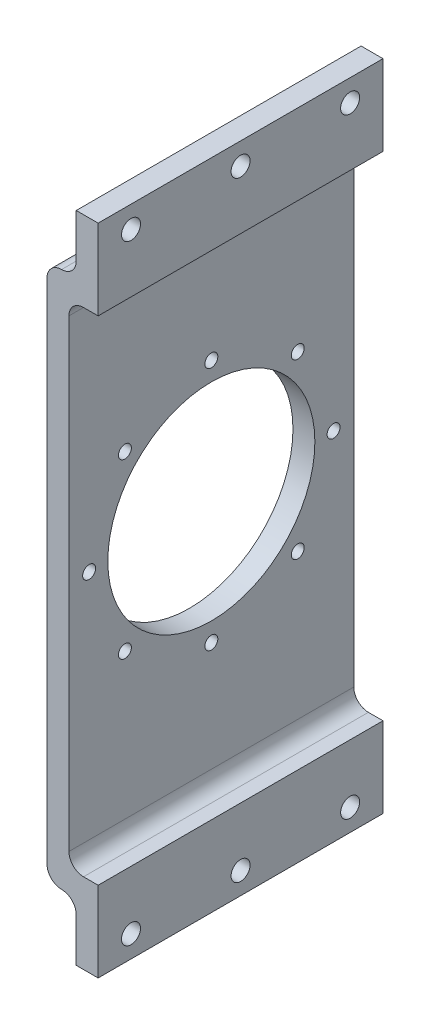
SolidWorks part; units mm, degrees
other "Markup1"
sketch "Sketch9" plane through (-7.62, -27.94, -49.53) normal (-1, 0, 0) x (0, 0, 1)
sketch "Sketch12" plane through (-7.62, -27.94, -49.53) normal (-1, 0, 0) x (0, 0, 1)
material "ABS"
ref_plane "Front Plane" through (0, 0, 0) normal (0, 0, 1) x (1, 0, 0)
ref_plane "Top Plane" through (0, 0, 0) normal (0, 1, 0) x (1, 0, 0)
ref_plane "Right Plane" through (0, 0, 0) normal (1, 0, 0) x (0, 0, -1)
sketch "Sketch1" plane through (0, 0, 0) normal (0, 0, 1) x (1, 0, 0)
  line L0 (0, 0) -> (0, 171.45)
  line L1 (0, 0) -> (10.16, 0)
  line L2 (-7.62, -7.62) -> (-7.62, 171.45)
  line L3 (-7.62, -7.62) -> (2.54, -7.62)
  line L5 (10.16, 0) -> (10.16, -7.62)
  line L8 (0, 171.45) -> (10.16, 171.45)
  line L9 (-7.62, 171.45) -> (-7.62, 179.07)
  line L10 (-7.62, 179.07) -> (2.54, 179.07)
  line L11 (10.16, 171.45) -> (10.16, 179.07)
  line L12 (10.16, -7.62) -> (10.16, -27.94)
  line L13 (10.16, -27.94) -> (2.54, -27.94)
  line L14 (2.54, -27.94) -> (2.54, -7.62)
  line L15 (10.16, 179.07) -> (10.16, 199.39)
  line L16 (-7.62, -7.62) -> (10.16, -7.62) construction
  line L17 (10.16, 199.39) -> (2.54, 199.39)
  line L18 (2.54, 199.39) -> (2.54, 179.07)
  point P7 (0, 0)
  point P12 (0, 0)
  dimension "D2" = 17.78
  dimension "D3" = 20.32
  dimension "D4" = 171.45
  dimension "D1" = 7.62
extrude "Boss-Extrude1" add sketch "Sketch1" along normal mid plane 99.06
ref_plane "Actuator Plane" through (0, 85.725, 0) normal (0, 1, 0) x (1, 0, 0)
fillet "Fillet1" radius 5.08 6 edges at (0, 0, 0) (2.54, -7.62, 0) (0, 171.45, 0) (2.54, 179.07, 0) (-7.62, 179.07, 0) (-7.62, -7.62, 0)
sketch "Sketch7" plane through (0, 0, 0) normal (1, 0, 0) x (0, 0, -1)
  line L0 (4.191, 85.725) -> (-4.191, 85.725) construction
  line L3 (-39.2649, 101.989) -> (0, 85.725) construction
  line L4 (0, 85.725) -> (-42.5, 85.725) construction
  circle A0 centre (0, 85.725) radius 42.5 construction
  circle A1 centre (-42.5, 85.725) radius 2.25
  circle A2 centre (-30.052, 115.777) radius 2.25
  circle A3 centre (0, 128.225) radius 2.25
  circle A4 centre (30.052, 115.777) radius 2.25
  circle A5 centre (42.5, 85.725) radius 2.25
  circle A6 centre (30.052, 55.673) radius 2.25
  circle A7 centre (0, 43.225) radius 2.25
  circle A8 centre (-30.052, 55.673) radius 2.25
  circle A9 centre (-39.2649, 101.989) radius 1.75 construction
  circle A10 centre (-16.264, 124.9899) radius 1.75 construction
  circle A11 centre (16.264, 124.9899) radius 1.75 construction
  circle A12 centre (39.2649, 101.989) radius 1.75 construction
  circle A13 centre (39.2649, 69.461) radius 1.75 construction
  circle A14 centre (16.264, 46.4601) radius 1.75 construction
  circle A15 centre (-16.264, 46.4601) radius 1.75 construction
  circle A16 centre (-39.2649, 69.461) radius 1.75 construction
  circle A17 centre (0, 85.725) radius 36
  point P28 (0, 85.725)
  point P45 (0, 85.725)
  dimension "D1" = 4.5
  dimension "D2" = 85
  dimension "D5" = 3.5
  dimension "D7" = 72
  dimension "D4" = 22.5
  dimension "D3" = 8
  dimension "D6" = 8
extrude "Cut-Extrude1" cut sketch "Sketch7" against normal up to surface (7.62 mm away) up to face at (-7.62, 85.725, 0)
sketch "Sketch8" plane through (2.54, 0, 0) normal (-1, 0, 0) x (0, 0, 1)
  line L0 (-38.1, 191.77) -> (0, 191.77) construction
  line L1 (0, 191.77) -> (38.1, 191.77) construction
  line L2 (0, -9.779) -> (0, 9.779) construction
  line L4 (-49.53, 199.39) -> (-49.53, 184.15) construction
  circle A0 centre (-38.1, 191.77) radius 3.302
  circle A1 centre (0, 191.77) radius 3.302
  circle A3 centre (38.1, 191.77) radius 3.302
  point P2 (0, 0)
  point P3 (19.1386, 191.77)
  point P4 (0, 0)
  point P17 (-49.53, 191.77)
  dimension "D4" = 6.604
  dimension "D2" = 76.2
extrude "Cut-Extrude2" cut sketch "Sketch8" against normal up to surface (7.62 mm away) up to face at (10.16, 185.42, 0)
mirror "Mirror1" about plane through (0, 85.725, 0) normal (0, 1, 0) of "Cut-Extrude2"
equation "\"VerticalHeight\"= 6.75"
equation "\"D4@Sketch1\"=\"VerticalHeight\""
